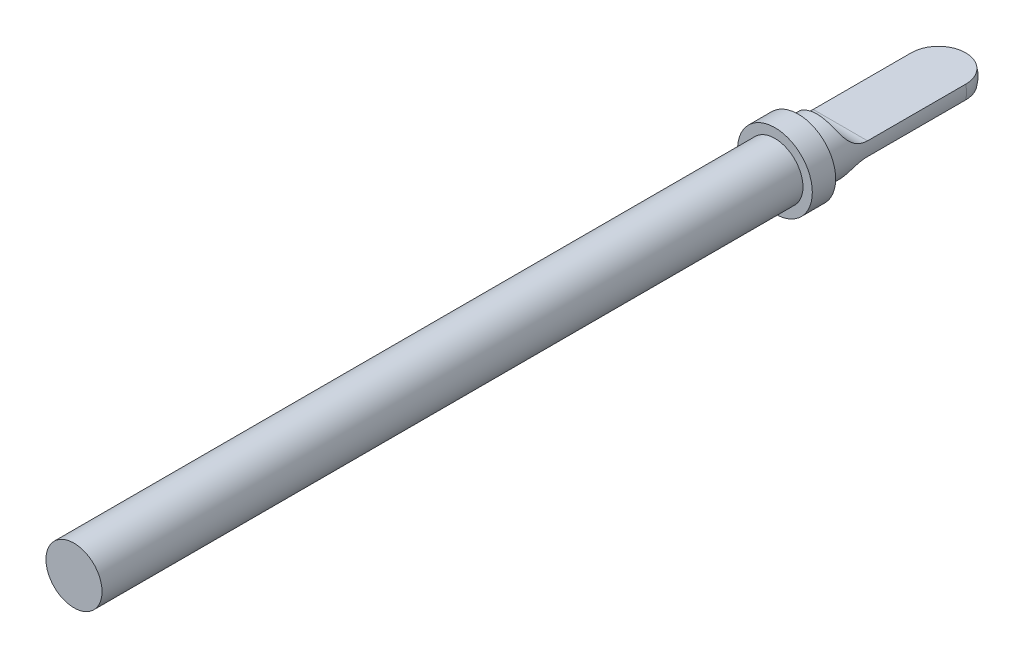
SolidWorks part; units mm, degrees
material "Hexcel AS4C (3000 丝)"
ref_plane "前视基准面" through (0, 0, 0) normal (0, 0, 1) x (1, 0, 0)
ref_plane "上视基准面" through (0, 0, 0) normal (0, 1, 0) x (1, 0, 0)
ref_plane "右视基准面" through (0, 0, 0) normal (1, 0, 0) x (0, 0, -1)
sketch "草图1" plane through (0, 0, 0) normal (0, 0, 1) x (1, 0, 0)
  circle A0 centre (0, 0) radius 6
extrude "凸台-拉伸1" add sketch "草图1" along normal blind 150
cosmetic thread "装饰螺纹线1" parameters "D2"=11
sketch "草图2" plane through (0, 0, 0) normal (0, 0, 1) x (1, 0, 0)
  circle A0 centre (0, 0) radius 8
extrude "凸台-拉伸2" add sketch "草图2" against normal blind 5
ref_plane "基准面1" through (0, 0, -5) normal (0, 0, -1) x (-1, 0, 0)
sketch "草图3" plane through (0, 0, -5) normal (0, 0, -1) x (-1, 0, 0)
  circle A0 centre (0, 0) radius 6
extrude "凸台-拉伸5" add sketch "草图3" along normal blind 30 contours A0
ref_plane "基准面4" through (0, 0, -35) normal (0, 0, -1) x (-1, 0, 0)
sketch "草图8" plane through (0, 0, -35) normal (0, 0, -1) x (-1, 0, 0)
  line L0 (0, 0) -> (0, -6) construction
  circle A0 centre (0, 0) radius 6
revolve "旋转8" add sketch "草图8" angle 360 about L0 region at (-4.1226, -4.1226, -35)
ref_plane "基准面5" through (0, 0, -9) normal (0, 0, -1) x (-1, 0, 0)
sketch "草图9" plane through (0, 0, -9) normal (0, 0, -1) x (-1, 0, 0)
  line L0 (0, 0) -> (9.0492, 0)
  line L1 (-8.8721, -7.2088) -> (10.3493, -7.2088)
  line L2 (-8.8721, 1.4635) -> (10.3493, 1.4635)
  line L3 (-8.8721, 1.4635) -> (-8.8721, 7.2088)
  line L4 (-8.8721, 7.2088) -> (10.3493, 7.2088)
  line L5 (10.3493, 1.4635) -> (10.3493, 7.2088)
  line L6 (10.3493, -1.4635) -> (10.3493, -7.2088)
  line L7 (-8.8721, -1.4635) -> (10.3493, -1.4635)
  line L8 (-8.8721, -1.4635) -> (-8.8721, -7.2088)
extrude "切除-拉伸7" cut sketch "草图9" along normal blind 40 contours L2 L5 L4 L3 | L7 L8 L1 L6 region at (-0.7386, -4.3361, -9) region at (-0.7386, 4.3361, -9)
fillet "圆角4" radius 5 1 edges at (0, 1.4635, -9)
fillet "圆角5" radius 5 1 edges at (0, -1.4635, -9)
